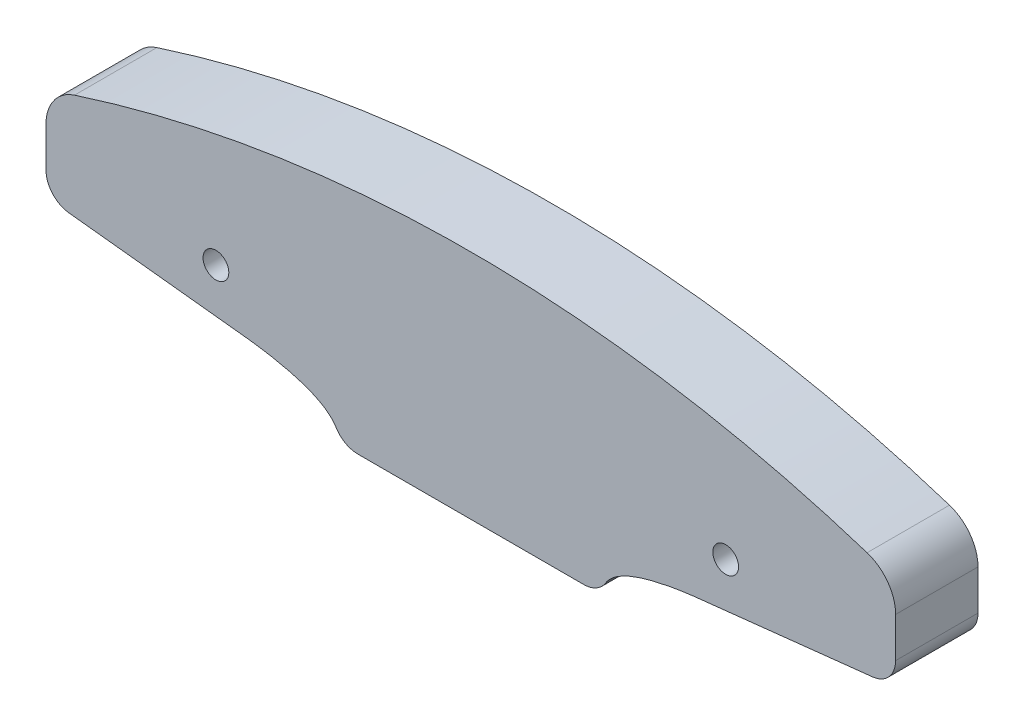
SolidWorks part; units mm, degrees
material "PUR"
ref_plane "Front" through (0, 0, 0) normal (0, 0, 1) x (1, 0, 0)
ref_plane "Top" through (0, 0, 0) normal (0, 1, 0) x (1, 0, 0)
ref_plane "Right" through (0, 0, 0) normal (1, 0, 0) x (0, 0, -1)
sketch "Sketch1" plane through (0, 0, 0) normal (0, 0, 1) x (1, 0, 0)
  line L0 (0, 0) -> (0, 45)
  line L1 (0, 45) -> (98.9481, 45) construction
  line L2 (82.5, 31) -> (82.5, 13)
  line L3 (82.5, 13) -> (15.5, 13) construction
  line L5 (25.5, 0) -> (0, 0)
  line L6 (25.5, 0) -> (25.5, 6.5) construction
  line L7 (82.5, 13) -> (43.1657, 8.6978)
  line L8 (25.5, 6.5) -> (43.1657, 8.6978) construction
  line L9 (25.5, 0) -> (25.5, 13) construction
  arc A0 (0, 45) -> (82.5, 31) centre (0, -205.0804) cw
  spline S0 degree 2 poles (25.5, 0) (25.5, 6.5) (43.1657, 8.6978) knots 0 0 0 1 1 1
  dimension "D1" = 45
  dimension "D2" = 57
  dimension "D3" = 18
  dimension "D4" = 13
  dimension "D5" = 82.5
extrude "Boss-Extrude1" add sketch "Sketch1" along normal blind 8 and the other way blind 8
mirror "Mirror1" about plane through (0, 0, 0) normal (1, 0, 0) of "Boss-Extrude1"
fillet "Fillet1" radius 8 2 edges at (82.5, 31, 0) (-82.5, 31, 0)
fillet "Fillet2" radius 5 2 edges at (82.5, 13, 0) (-82.5, 13, 0)
fillet "Fillet3" radius 5 2 edges at (25.5, 0, 0) (-25.5, 0, 0)
sketch "Sketch2" plane through (0, 0, 8) normal (0, 0, 1) x (1, 0, 0)
  line L0 (82.5, 17.4829) -> (82.5, 25.2513) construction
  line L1 (-21.9184, 0) -> (21.9184, 0) construction
  circle A0 centre (49.5, 18) radius 2.5
  dimension "D1" = 5
  dimension "D2" = 33
  dimension "D3" = 18
extrude "Cut-Extrude1" cut sketch "Sketch2" against normal through all
mirror "Mirror4" about plane through (0, 0, 0) normal (1, 0, 0) of "Cut-Extrude1"
